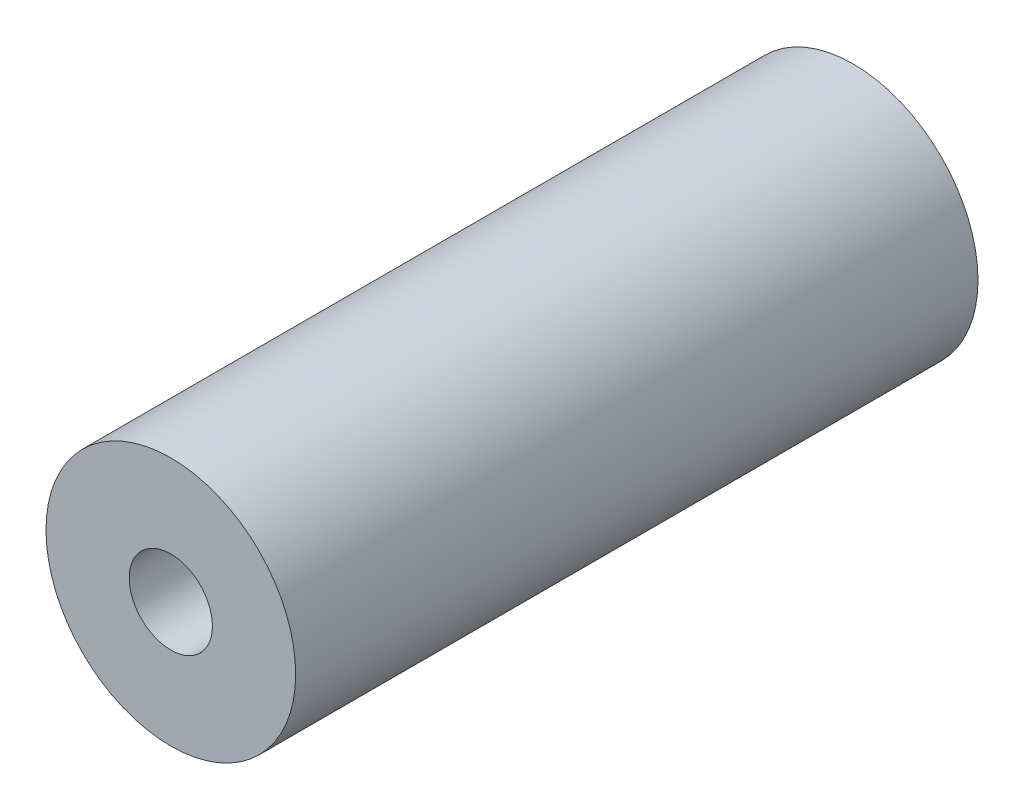
SolidWorks part; units mm, degrees
material "Polyurethane Foam Flexible"
ref_plane "Front" through (0, 0, 0) normal (0, 0, 1) x (1, 0, 0)
ref_plane "Top" through (0, 0, 0) normal (0, 1, 0) x (1, 0, 0)
ref_plane "Right" through (0, 0, 0) normal (1, 0, 0) x (0, 0, -1)
sketch "Sketch1" plane through (0, 0, 0) normal (0, 0, 1) x (1, 0, 0)
  circle A0 centre (0, 0) radius 3.175
  circle A1 centre (0, 0) radius 9.525
  dimension "D1" = 6.35
  dimension "D2" = 19.05
extrude "Boss-Extrude1" add sketch "Sketch1" along normal blind 52.07
